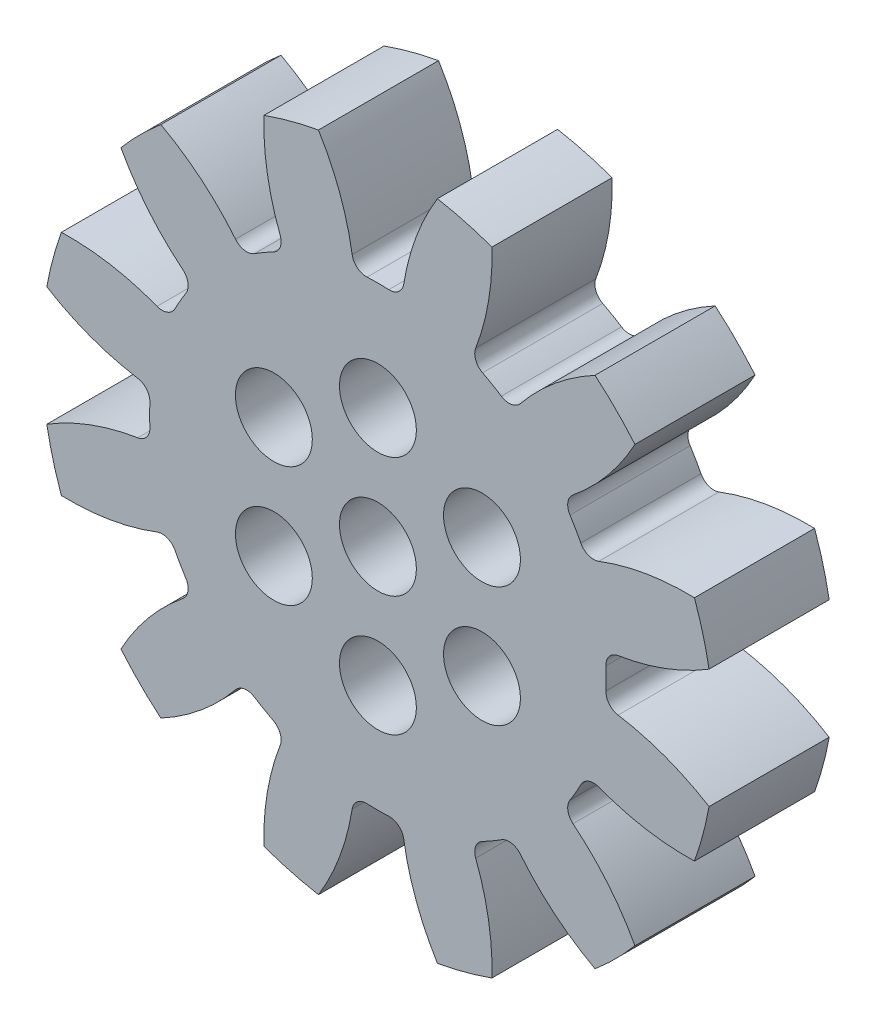
SolidWorks part; units mm, degrees
ref_plane "Front Plane" through (0, 0, 0) normal (0, 0, 1) x (1, 0, 0)
ref_plane "Top Plane" through (0, 0, 0) normal (0, 1, 0) x (1, 0, 0)
ref_plane "Right Plane" through (0, 0, 0) normal (1, 0, 0) x (0, 0, -1)
sketch "Sketch1" plane through (0, 0, 0) normal (0, 0, 1) x (1, 0, 0)
  circle A0 centre (0, 0) radius 12
  circle A1 centre (0, 0) radius 9.5
  circle A2 centre (0, 0) radius 14
  dimension "D1" = 24
  dimension "D2" = 28
  dimension "D3" = 4.5
extrude "Boss-Extrude1" add sketch "Sketch1" along normal mid plane 5 contours A2
sketch "Sketch2" plane through (0, 0, 0) normal (0, 0, 1) x (1, 0, 0)
  line L0 (0, 0) -> (0, 14) construction
  line L1 (-0.9997, 9.4472) -> (0, 0) construction
  line L2 (-1.5663, 11.8973) -> (1.5663, 11.8973) construction
  line L3 (0, 7.5939) -> (-2.7213, 15.0705) construction
  line L4 (0, 0) -> (3.6235, 13.523) construction
  line L5 (1.5663, 11.8973) -> (4.5922, 11.0866) construction
  circle A0 centre (0, 0) radius 14 construction
  arc A1 (-3.3146, 14.9512) -> (-0.9997, 9.4472) centre (-11.2897, 8.3583) cw
  arc A2 (3.3146, 14.9512) -> (0.9997, 9.4472) centre (11.2897, 8.3583) ccw
  arc A3 (3.3146, 14.9512) -> (-3.3146, 14.9512) centre (0, 0) ccw
  arc A4 (0.9997, 9.4472) -> (-0.9997, 9.4472) centre (0, 0) ccw
  circle A6 centre (0, 0) radius 9.5 construction
  circle A7 centre (0, 0) radius 12 construction
  dimension "D1" = 20
  dimension "D2" = 15
extrude "Cut-Extrude1" cut sketch "Sketch2" against normal through all both and the other way through all
fillet "Fillet1" radius 0.6 1 edges at (-0.9997, 9.4472, 0) type face fillet first side face at (-1.6166, 11.6546, 0) second side face at (0, 9.4736, 0)
fillet "Fillet2" radius 0.6 1 edges at (0.9997, 9.4472, 0) type face fillet first side face at (1.6166, 11.6546, 0) second side face at (0.2746, 9.4821, 0)
sketch "Sketch3" plane through (0, 0, 2.5) normal (0, 0, 1) x (1, 0, 0)
pattern_circular "CirPattern2" count 12 over 360 about axis through (0, 0, 2.5) along (0, 0, 1) of "Fillet1", "Cut-Extrude1", "Fillet2"
sketch "Sketch4" plane through (0, 0, 2.5) normal (0, 0, 1) x (1, 0, 0)
  line L0 (0, 0) -> (0, 8.1574) construction
  circle A0 centre (0, 0) radius 1.5
  circle A1 centre (0, 5) radius 1.5
  circle A2 centre (4.3301, 2.5) radius 1.5
  circle A3 centre (4.3301, -2.5) radius 1.5
  circle A4 centre (0, -5) radius 1.5
  circle A5 centre (-4.3301, -2.5) radius 1.5
  circle A6 centre (-4.3301, 2.5) radius 1.5
  point P18 (0, 0)
  dimension "D1" = 3
  dimension "D2" = 3
  dimension "D3" = 5
  dimension "D4" = 6
extrude "Cut-Extrude2" cut sketch "Sketch4" against normal through all both and the other way through all
sketch "Sketch5" plane through (0, 0, 2.5) normal (0, 0, 1) x (1, 0, 0)
  circle A0 centre (0, 5) radius 1.6
  circle A1 centre (-4.3301, -2.5) radius 1.5
  circle A2 centre (-4.3301, -2.5) radius 1.5 construction
  circle A3 centre (0, -5) radius 1.5
  circle A4 centre (0, -5) radius 1.5 construction
  circle A5 centre (4.3301, -2.5) radius 1.5
  circle A6 centre (4.3301, -2.5) radius 1.5 construction
  circle A7 centre (4.3301, 2.5) radius 1.5
  circle A8 centre (4.3301, 2.5) radius 1.5 construction
  circle A9 centre (0, 5) radius 1.5
  circle A10 centre (0, 5) radius 1.5 construction
  circle A11 centre (0, 0) radius 1.5
  circle A12 centre (0, 0) radius 1.5 construction
  circle A13 centre (-4.3301, 2.5) radius 1.5
  circle A14 centre (-4.3301, 2.5) radius 1.5 construction
  circle A15 centre (4.3301, 2.5) radius 1.6
  circle A16 centre (4.3301, -2.5) radius 1.6
  circle A17 centre (0, -5) radius 1.6
  circle A18 centre (0, 0) radius 1.6
  circle A19 centre (-4.3301, -2.5) radius 1.6
  circle A20 centre (-4.3301, 2.5) radius 1.6
  dimension "D8" = 3.2
  dimension "D1" = 0
  dimension "D2" = 0
  dimension "D3" = 0
  dimension "D4" = 0
  dimension "D5" = 0
  dimension "D6" = 0
  dimension "D7" = 0
extrude "Cut-Extrude3" cut sketch "Sketch5" against normal through all
equation "\"Number of Teeth\"= 12"
equation "\"Module\"= 2mm"
equation "\"D2@Sketch2\"=180 / \"Number of Teeth\""
equation "\"D1@Sketch1\"= \"Module\" * \"Number of Teeth\""
equation "\"D2@Sketch1\"=(\"Number of Teeth\" + 2) * \"Module\""
equation "\"D3@Sketch1\"= \"Module\" * 2.25"
equation "\"D1@CirPattern2\"= \"Number of Teeth\""
